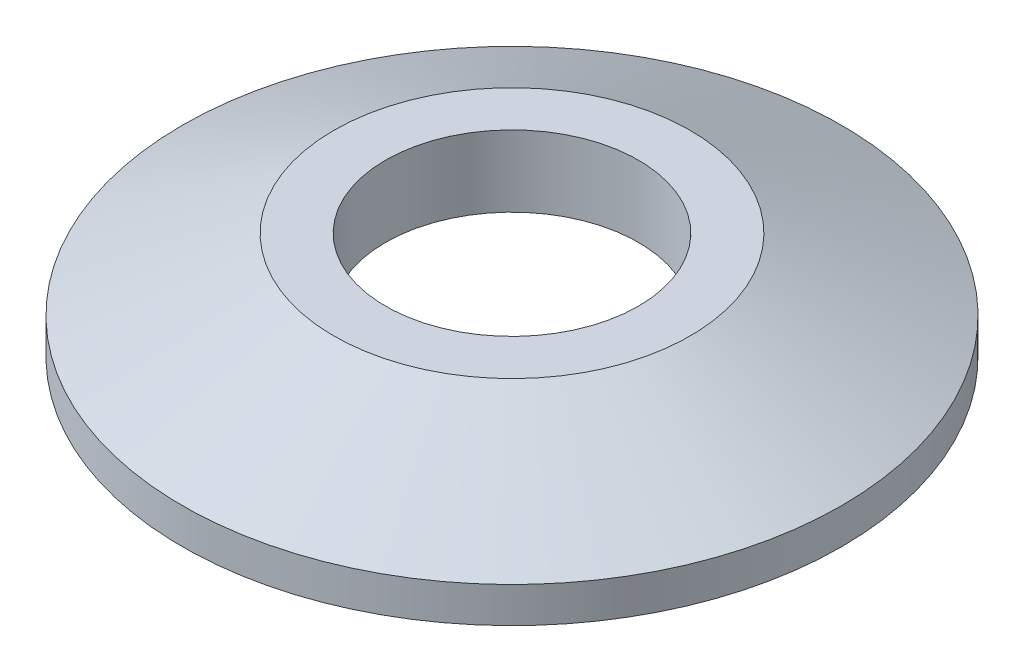
SolidWorks part; units mm, degrees
material "Plain Carbon Steel"
ref_plane "Front Plane" through (0, 0, 0) normal (0, 0, 1) x (1, 0, 0)
ref_plane "Top Plane" through (0, 0, 0) normal (0, 1, 0) x (1, 0, 0)
ref_plane "Right Plane" through (0, 0, 0) normal (1, 0, 0) x (0, 0, -1)
sketch "Sketch1" plane through (0, 0, 0) normal (0, 0, 1) x (1, 0, 0)
  line L0 (-18.5, 0) -> (-18.5, 2)
  line L1 (-18.5, 2) -> (-10, 6)
  line L2 (-10, 6) -> (-7.1, 6)
  line L3 (-7.1, 6) -> (-7.1, 2)
  line L4 (-7.1, 2) -> (-10, 2)
  line L5 (-10, 2) -> (-10, 0)
  line L6 (-10, 0) -> (-18.5, 0)
  line L7 (0, 22.2676) -> (0, -14.7324) construction
  point P10 (0, 0)
  dimension "D1" = 14.2
  dimension "D2" = 20
  dimension "D3" = 20
  dimension "D4" = 37
  dimension "D5" = 2
  dimension "D6" = 6
revolve "Revolve1" add sketch "Sketch1" angle 360 about L7
